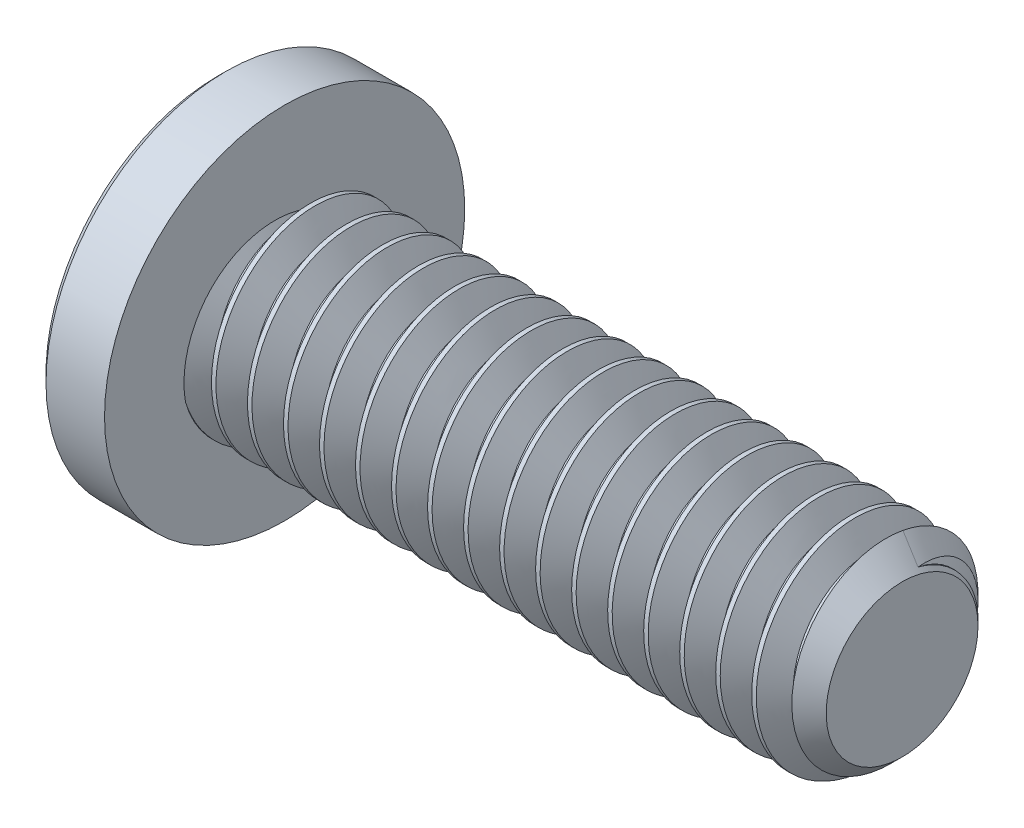
SolidWorks part; units mm, degrees
ref_plane "Front Plane" through (0, 0, 0) normal (0, 0, 1) x (1, 0, 0)
ref_plane "Top Plane" through (0, 0, 0) normal (0, 1, 0) x (1, 0, 0)
ref_plane "Right Plane" through (0, 0, 0) normal (1, 0, 0) x (0, 0, -1)
sketch "Sketch1" plane through (0, 0, 0) normal (0, 0, 1) x (1, 0, 0)
  line L0 (6, 0) -> (-6, 0) construction
  line L1 (6, 2) -> (6, -2) construction
  line L2 (-6, 3.5) -> (-6, -3.5) construction
  line L3 (-6, 3.5) -> (-7.1375, 3.5) construction
  line L4 (-7.1375, 3.5) -> (-7.3, 3.3375) construction
  line L5 (-7.3, 3.3375) -> (-7.3, -3.3375) construction
  line L6 (-7.3, -3.3375) -> (-7.1375, -3.5) construction
  line L7 (-7.1375, -3.5) -> (-6, -3.5) construction
  point P7 (-4.88, 0)
  point P12 (3.2, -2)
  dimension "D1" = 45
  dimension "Dec." = 4
  dimension "Length" = 12
  dimension "Head Dia" = 7
  dimension "Head Height" = 1.3
  dimension "Hex Depth" = 2.42
  dimension "Chamfer" = 0.1625
  dimension "D2" = 2.8
ref_plane "Plane1" through (6, 0, 0) normal (1, 0, 0) x (0, 0, -1)
ref_plane "Plane2" through (-7.3, 0, 0) normal (1, 0, 0) x (0, 0, -1)
sketch "Sketch2" plane through (6, 0, 0) normal (1, 0, 0) x (0, 0, -1)
  circle A0 centre (0, 0) radius 2
extrude "Boss-Extrude1" add sketch "Sketch2" against normal up to vertex (12 mm away) up to point (-6, 0, 0)
sketch "Sketch3" plane through (6, 0, 0) normal (1, 0, 0) x (0, 0, -1)
  circle A0 centre (0, 0) radius 2 construction
  circle A1 centre (0, 0) radius 2
curve "Helix/Spiral1" pitch 0.7 height 12.7 radius 2 centre (6, 0, 0) axis (-1, 0, 0) start towards (0, 1, 0) parameters "Pitch"=0.7
chamfer "Chamfer1" distance 0.525 angle 45 1 edges at (6, 0, -2)
sketch "Sketch5" plane through (0, 0, 0) normal (0, 0, 1) x (1, 0, 0)
  line L0 (5.6937, 2) -> (6.3062, 2)
  line L1 (6.3062, 2) -> (6.0437, 1.5453)
  line L2 (6.0437, 1.5453) -> (5.9562, 1.5453)
  line L3 (5.9562, 1.5453) -> (5.6937, 2)
  line L4 (6, 1.5453) -> (6, 2) construction
  line L5 (5.825, 1.7727) -> (6.175, 1.7727) construction
  dimension "D1" = 60
  dimension "D2" = 0.35
  dimension "D3" = 0.0875
sweep "Cut-Sweep1" cut profiles "Sketch5" path "Helix/Spiral1" align with end faces yes
sketch "Sketch4" plane through (-7.3, 0, 0) normal (1, 0, 0) x (0, 0, -1)
  line L0 (-3.5, 0.7937) -> (3.5, 0.7937) construction
  line L1 (0, 1.4434) -> (-1.25, 0.7217)
  line L2 (-1.25, 0.7217) -> (-1.25, -0.7217)
  line L3 (-1.25, -0.7217) -> (0, -1.4434)
  line L4 (0, -1.4434) -> (1.25, -0.7217)
  line L5 (1.25, -0.7217) -> (1.25, 0.7217)
  line L6 (1.25, 0.7217) -> (0, 1.4434)
  line L7 (0, 0) -> (0, 0.7937) construction
  circle A0 centre (0, 0) radius 1.25 construction
  dimension "Hex Size" = 2.5
  dimension "D1" = 7
  dimension "D2" = 0.7937
sketch "Sketch6" plane through (0, 0, 0) normal (0, 0, 1) x (1, 0, 0)
  line L0 (-7.1375, 3.5) -> (-7.3, 3.3375) construction
  line L1 (-6, 3.5) -> (-7.1375, 3.5) construction
  line L2 (-6, 3.5) -> (-6, -3.5) construction
  line L3 (-7.3, 3.3375) -> (-7.3, -3.3375) construction
  line L4 (-7.1375, 3.5) -> (-7.3, 3.3375)
  line L5 (-6, 3.5) -> (-7.1375, 3.5)
  line L6 (-6, 3.5) -> (-6, 0)
  line L7 (-7.3, 3.3375) -> (-7.3, 0)
  line L8 (-6, 0) -> (-7.3, 0) construction
  line L9 (-6, 0) -> (-7.3, 0)
revolve "Revolve1" add sketch "Sketch6" angle 360 about L8
extrude "Cut-Extrude1" cut sketch "Sketch4" along normal up to vertex (2.42 mm away) up to point (-4.88, 0, 0)
sketch "Sketch8" plane through (-7.3, 0, 0) normal (-1, 0, 0) x (0, 0, 1)
  circle A1 centre (0, 0) radius 1.4434
extrude "Cut-Extrude2" cut sketch "Sketch8" against normal through all draft 45
equation "\"D3@Helix/Spiral1\" = \"Length@Sketch1\"+\"Pitch@Helix/Spiral1\""
equation "\"D3@Sketch5\" = \"Pitch@Helix/Spiral1\"*.125"
equation "\"D2@Sketch5\" = \"Pitch@Helix/Spiral1\"*.50"
equation "\"D1@Chamfer1\" = \"Pitch@Helix/Spiral1\"*.75"
equation "\"D2@Sketch1\" = \"Pitch@Helix/Spiral1\"*4"
equation "\"D1@Sketch4\" = \"Head Dia@Sketch1\""
equation "\"Chamfer@Sketch1\" = \"Head Height@Sketch1\"/8"
